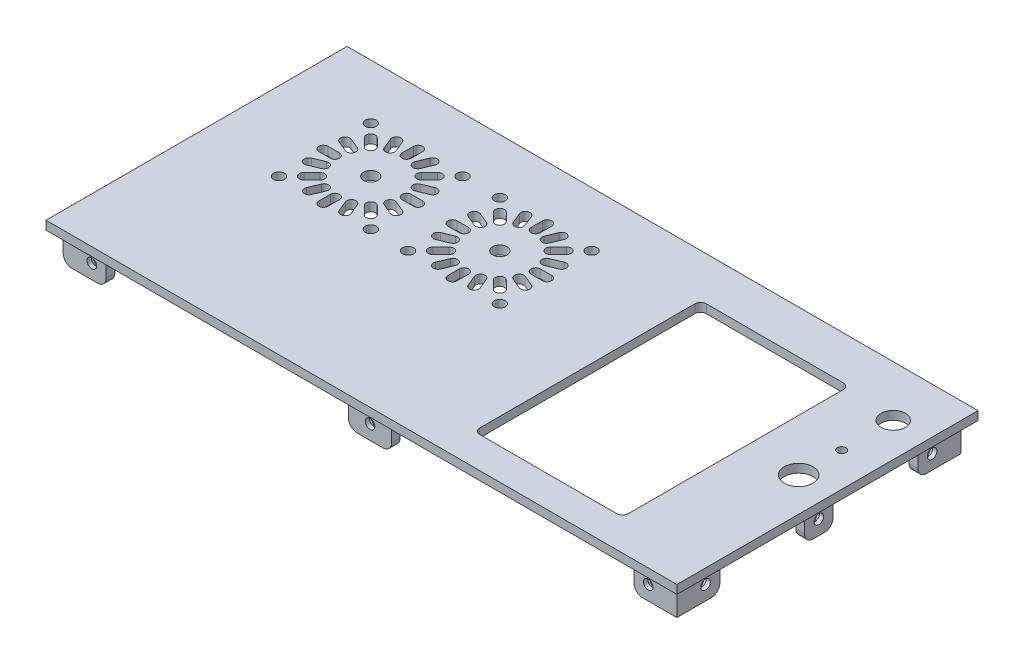
SolidWorks part; units mm, degrees
ref_plane "Ön Düzlem" through (0, 0, 0) normal (0, 0, 1) x (1, 0, 0)
ref_plane "Üst Düzlem" through (0, 0, 0) normal (0, 1, 0) x (1, 0, 0)
ref_plane "Sağ Düzlem" through (0, 0, 0) normal (1, 0, 0) x (0, 0, -1)
sketch "Çizim1" plane through (0, 0, 0) normal (0, 1, 0) x (1, 0, 0)
  line L0 (-66.65, 17.4) -> (49933.35, 17.4) construction
  line L1 (-110, -52.5) -> (110, -52.5)
  line L2 (-110, -52.5) -> (-110, 52.5)
  line L3 (-110, 52.5) -> (110, 52.5)
  line L4 (110, -52.5) -> (110, 52.5)
  line L5 (-110, -52.5) -> (110, 52.5) construction
  line L6 (-110, 52.5) -> (110, -52.5) construction
  line L7 (78.15, 37.4) -> (30.35, 37.4)
  line L8 (80.15, 35.4) -> (80.15, -39.6)
  line L9 (78.15, -41.6) -> (30.35, -41.6)
  line L10 (28.35, 35.4) -> (28.35, -39.6)
  line L11 (80.15, 37.4) -> (28.35, -41.6) construction
  line L12 (80.15, -41.6) -> (28.35, 37.4) construction
  line L13 (-66.65, 17.4) -> (-66.65, 50017.4) construction
  line L14 (-44.15, 43.0126) -> (-44.15, -49956.9874) construction
  line L15 (-66.65, 17.4) -> (35288.6891, -35337.9391) construction
  line L16 (-66.65, 17.4) -> (35288.6891, 35372.7391) construction
  line L17 (-66.65, 17.4) -> (19067.5216, -46176.5766) construction
  line L18 (-66.65, 17.4) -> (19067.5216, 46211.3766) construction
  line L19 (-66.65, 17.4) -> (46127.3266, -19116.7716) construction
  line L20 (-66.65, 17.4) -> (46127.3266, 19151.5716) construction
  line L21 (-66.65, 29.9) -> (-66.65, 33.9) construction
  line L22 (-68.25, 29.9) -> (-68.25, 33.9)
  line L23 (-65.05, 29.9) -> (-65.05, 33.9)
  line L24 (-71.4335, 28.9485) -> (-72.9643, 32.644) construction
  line L25 (-72.9118, 28.3362) -> (-74.4425, 32.0317)
  line L26 (-69.9553, 29.5608) -> (-71.4861, 33.2563)
  line L27 (-79.15, 17.4) -> (-83.15, 17.4) construction
  line L28 (-79.15, 19) -> (-83.15, 19)
  line L29 (-79.15, 15.8) -> (-83.15, 15.8)
  line L30 (-78.1985, 22.1835) -> (-81.894, 23.7143) construction
  line L31 (-77.5862, 23.6618) -> (-81.2817, 25.1925)
  line L32 (-78.8108, 20.7053) -> (-82.5063, 22.2361)
  line L33 (-75.4888, 26.2388) -> (-78.3173, 29.0673) construction
  line L34 (-74.3575, 27.3702) -> (-77.1859, 30.1986)
  line L35 (-76.6202, 25.1075) -> (-79.4486, 27.9359)
  line L36 (-78.1985, 12.6165) -> (-81.894, 11.0857) construction
  line L37 (-77.5862, 11.1382) -> (-81.2817, 9.6075)
  line L38 (-78.8108, 14.0947) -> (-82.5063, 12.5639)
  line L39 (-75.4888, 8.5612) -> (-78.3173, 5.7327) construction
  line L40 (-74.3575, 7.4298) -> (-77.1859, 4.6014)
  line L41 (-76.6202, 9.6925) -> (-79.4486, 6.8641)
  line L42 (-71.4335, 5.8515) -> (-72.9643, 2.156) construction
  line L43 (-72.9118, 6.4638) -> (-74.4425, 2.7683)
  line L44 (-69.9553, 5.2392) -> (-71.4861, 1.5437)
  line L45 (-66.65, 4.9) -> (-66.65, 0.9) construction
  line L46 (-68.25, 4.9) -> (-68.25, 0.9)
  line L47 (-65.05, 4.9) -> (-65.05, 0.9)
  line L48 (-54.15, 17.4) -> (-50.15, 17.4) construction
  line L49 (-54.15, 19) -> (-50.15, 19)
  line L50 (-54.15, 15.8) -> (-50.15, 15.8)
  line L51 (-55.1015, 22.1835) -> (-51.406, 23.7143) construction
  line L52 (-55.7138, 23.6618) -> (-52.0183, 25.1925)
  line L53 (-54.4892, 20.7053) -> (-50.7937, 22.2361)
  line L54 (-57.8112, 26.2388) -> (-54.9827, 29.0673) construction
  line L55 (-58.9425, 27.3702) -> (-56.1141, 30.1986)
  line L56 (-56.6798, 25.1075) -> (-53.8514, 27.9359)
  line L57 (-61.8665, 28.9485) -> (-60.3357, 32.644) construction
  line L58 (-60.3882, 28.3362) -> (-58.8575, 32.0317)
  line L59 (-63.3447, 29.5608) -> (-61.8139, 33.2563)
  line L60 (-55.1015, 12.6165) -> (-51.406, 11.0857) construction
  line L61 (-55.7138, 11.1382) -> (-52.0183, 9.6075)
  line L62 (-54.4892, 14.0947) -> (-50.7937, 12.5639)
  line L63 (-57.8112, 8.5612) -> (-54.9827, 5.7327) construction
  line L64 (-58.9425, 7.4298) -> (-56.1141, 4.6014)
  line L65 (-56.6798, 9.6925) -> (-53.8514, 6.8641)
  line L66 (-61.8665, 5.8515) -> (-60.3357, 2.156) construction
  line L67 (-60.3882, 6.4638) -> (-58.8575, 2.7683)
  line L68 (-63.3447, 5.2392) -> (-61.8139, 1.5437)
  line L69 (-16.8665, 28.9485) -> (-15.3357, 32.644) construction
  line L70 (-15.3882, 28.3362) -> (-13.8575, 32.0317)
  line L71 (-18.3447, 29.5608) -> (-16.8139, 33.2563)
  line L72 (-12.8112, 26.2388) -> (-9.9827, 29.0673) construction
  line L73 (-13.9425, 27.3702) -> (-11.1141, 30.1986)
  line L74 (-11.6798, 25.1075) -> (-8.8514, 27.9359)
  line L75 (-10.1015, 22.1835) -> (-6.406, 23.7143) construction
  line L76 (-10.7138, 23.6618) -> (-7.0183, 25.1925)
  line L77 (-9.4892, 20.7053) -> (-5.7937, 22.2361)
  line L78 (-9.15, 17.4) -> (-5.15, 17.4) construction
  line L79 (-9.15, 19) -> (-5.15, 19)
  line L80 (-9.15, 15.8) -> (-5.15, 15.8)
  line L81 (-10.1015, 12.6165) -> (-6.406, 11.0857) construction
  line L82 (-10.7138, 11.1382) -> (-7.0183, 9.6075)
  line L83 (-9.4892, 14.0947) -> (-5.7937, 12.5639)
  line L84 (-12.8112, 8.5612) -> (-9.9827, 5.7327) construction
  line L85 (-13.9425, 7.4298) -> (-11.1141, 4.6014)
  line L86 (-11.6798, 9.6925) -> (-8.8514, 6.8641)
  line L87 (-16.8665, 5.8515) -> (-15.3357, 2.156) construction
  line L88 (-15.3882, 6.4638) -> (-13.8575, 2.7683)
  line L89 (-18.3447, 5.2392) -> (-16.8139, 1.5437)
  line L90 (-21.65, 4.9) -> (-21.65, 0.9) construction
  line L91 (-20.05, 4.9) -> (-20.05, 0.9)
  line L92 (-23.25, 4.9) -> (-23.25, 0.9)
  line L93 (-21.65, 29.9) -> (-21.65, 33.9) construction
  line L94 (-20.05, 29.9) -> (-20.05, 33.9)
  line L95 (-23.25, 29.9) -> (-23.25, 33.9)
  line L96 (-26.4335, 5.8515) -> (-27.9643, 2.156) construction
  line L97 (-27.9118, 6.4638) -> (-29.4425, 2.7683)
  line L98 (-24.9553, 5.2392) -> (-26.4861, 1.5437)
  line L99 (-30.4888, 8.5612) -> (-33.3173, 5.7327) construction
  line L100 (-29.3575, 7.4298) -> (-32.1859, 4.6014)
  line L101 (-31.6202, 9.6925) -> (-34.4486, 6.8641)
  line L102 (-33.1985, 12.6165) -> (-36.894, 11.0857) construction
  line L103 (-32.5862, 11.1382) -> (-36.2817, 9.6075)
  line L104 (-33.8108, 14.0947) -> (-37.5063, 12.5639)
  line L105 (-34.15, 17.4) -> (-38.15, 17.4) construction
  line L106 (-34.15, 19) -> (-38.15, 19)
  line L107 (-34.15, 15.8) -> (-38.15, 15.8)
  line L108 (-33.1985, 22.1835) -> (-36.894, 23.7143) construction
  line L109 (-32.5862, 23.6618) -> (-36.2817, 25.1925)
  line L110 (-33.8108, 20.7053) -> (-37.5063, 22.2361)
  line L111 (-30.4888, 26.2388) -> (-33.3173, 29.0673) construction
  line L112 (-29.3575, 27.3702) -> (-32.1859, 30.1986)
  line L113 (-31.6202, 25.1075) -> (-34.4486, 27.9359)
  line L114 (-26.4335, 28.9485) -> (-27.9643, 32.644) construction
  line L115 (-27.9118, 28.3362) -> (-29.4425, 32.0317)
  line L116 (-24.9553, 29.5608) -> (-26.4861, 33.2563)
  circle A0 centre (98.15, 34.8) radius 4.25
  circle A1 centre (98.15, 1.8) radius 5
  circle A2 centre (98.15, 16.8) radius 1.5
  arc A3 (-15.3882, 28.3362) -> (-18.3447, 29.5608) centre (-16.8665, 28.9485) cw
  circle A5 centre (-82.65, 33.4) radius 1.9
  circle A6 centre (-50.65, 33.4) radius 1.9
  circle A7 centre (-37.65, 33.4) radius 1.9
  circle A8 centre (-5.65, 33.4) radius 1.9
  circle A9 centre (-5.65, 1.4) radius 1.9
  circle A10 centre (-37.65, 1.4) radius 1.9
  circle A11 centre (-50.65, 1.4) radius 1.9
  circle A12 centre (-82.65, 1.4) radius 1.9
  arc A13 (80.15, -39.6) -> (78.15, -41.6) centre (78.15, -39.6) cw
  arc A14 (30.35, -41.6) -> (28.35, -39.6) centre (30.35, -39.6) cw
  arc A15 (80.15, 35.4) -> (78.15, 37.4) centre (78.15, 35.4) ccw
  arc A16 (30.35, 37.4) -> (28.35, 35.4) centre (30.35, 35.4) ccw
  arc A17 (-16.8139, 33.2563) -> (-13.8575, 32.0317) centre (-15.3357, 32.644) cw
  arc A18 (-13.9425, 27.3702) -> (-11.6798, 25.1075) centre (-12.8112, 26.2388) ccw
  arc A19 (-68.25, 29.9) -> (-65.05, 29.9) centre (-66.65, 29.9) ccw
  arc A20 (-65.05, 33.9) -> (-68.25, 33.9) centre (-66.65, 33.9) ccw
  arc A21 (-72.9118, 28.3362) -> (-69.9553, 29.5608) centre (-71.4335, 28.9485) ccw
  arc A22 (-71.4861, 33.2563) -> (-74.4425, 32.0317) centre (-72.9643, 32.644) ccw
  arc A23 (-79.15, 19) -> (-79.15, 15.8) centre (-79.15, 17.4) cw
  arc A24 (-83.15, 15.8) -> (-83.15, 19) centre (-83.15, 17.4) cw
  arc A25 (-77.5862, 23.6618) -> (-78.8108, 20.7053) centre (-78.1985, 22.1835) cw
  arc A26 (-82.5063, 22.2361) -> (-81.2817, 25.1925) centre (-81.894, 23.7143) cw
  arc A27 (-74.3575, 27.3702) -> (-76.6202, 25.1075) centre (-75.4888, 26.2388) cw
  arc A28 (-79.4486, 27.9359) -> (-77.1859, 30.1986) centre (-78.3173, 29.0673) cw
  arc A29 (-77.5862, 11.1382) -> (-78.8108, 14.0947) centre (-78.1985, 12.6165) ccw
  arc A30 (-82.5063, 12.5639) -> (-81.2817, 9.6075) centre (-81.894, 11.0857) ccw
  arc A31 (-74.3575, 7.4298) -> (-76.6202, 9.6925) centre (-75.4888, 8.5612) ccw
  arc A32 (-79.4486, 6.8641) -> (-77.1859, 4.6014) centre (-78.3173, 5.7327) ccw
  arc A33 (-72.9118, 6.4638) -> (-69.9553, 5.2392) centre (-71.4335, 5.8515) cw
  arc A34 (-71.4861, 1.5437) -> (-74.4425, 2.7683) centre (-72.9643, 2.156) cw
  arc A35 (-68.25, 4.9) -> (-65.05, 4.9) centre (-66.65, 4.9) cw
  arc A36 (-65.05, 0.9) -> (-68.25, 0.9) centre (-66.65, 0.9) cw
  arc A37 (-54.15, 19) -> (-54.15, 15.8) centre (-54.15, 17.4) ccw
  arc A38 (-50.15, 15.8) -> (-50.15, 19) centre (-50.15, 17.4) ccw
  arc A39 (-55.7138, 23.6618) -> (-54.4892, 20.7053) centre (-55.1015, 22.1835) ccw
  arc A40 (-50.7937, 22.2361) -> (-52.0183, 25.1925) centre (-51.406, 23.7143) ccw
  arc A41 (-58.9425, 27.3702) -> (-56.6798, 25.1075) centre (-57.8112, 26.2388) ccw
  arc A42 (-53.8514, 27.9359) -> (-56.1141, 30.1986) centre (-54.9827, 29.0673) ccw
  arc A43 (-60.3882, 28.3362) -> (-63.3447, 29.5608) centre (-61.8665, 28.9485) cw
  arc A44 (-61.8139, 33.2563) -> (-58.8575, 32.0317) centre (-60.3357, 32.644) cw
  arc A45 (-55.7138, 11.1382) -> (-54.4892, 14.0947) centre (-55.1015, 12.6165) cw
  arc A46 (-50.7937, 12.5639) -> (-52.0183, 9.6075) centre (-51.406, 11.0857) cw
  arc A47 (-58.9425, 7.4298) -> (-56.6798, 9.6925) centre (-57.8112, 8.5612) cw
  arc A48 (-53.8514, 6.8641) -> (-56.1141, 4.6014) centre (-54.9827, 5.7327) cw
  arc A49 (-60.3882, 6.4638) -> (-63.3447, 5.2392) centre (-61.8665, 5.8515) ccw
  arc A50 (-61.8139, 1.5437) -> (-58.8575, 2.7683) centre (-60.3357, 2.156) ccw
  circle A51 centre (-66.65, 17.4) radius 2.5
  arc A52 (-8.8514, 27.9359) -> (-11.1141, 30.1986) centre (-9.9827, 29.0673) ccw
  arc A53 (-10.7138, 23.6618) -> (-9.4892, 20.7053) centre (-10.1015, 22.1835) ccw
  arc A54 (-5.7937, 22.2361) -> (-7.0183, 25.1925) centre (-6.406, 23.7143) ccw
  arc A55 (-9.15, 19) -> (-9.15, 15.8) centre (-9.15, 17.4) ccw
  arc A56 (-5.15, 15.8) -> (-5.15, 19) centre (-5.15, 17.4) ccw
  arc A57 (-10.7138, 11.1382) -> (-9.4892, 14.0947) centre (-10.1015, 12.6165) cw
  arc A58 (-5.7937, 12.5639) -> (-7.0183, 9.6075) centre (-6.406, 11.0857) cw
  arc A59 (-13.9425, 7.4298) -> (-11.6798, 9.6925) centre (-12.8112, 8.5612) cw
  arc A60 (-8.8514, 6.8641) -> (-11.1141, 4.6014) centre (-9.9827, 5.7327) cw
  arc A61 (-15.3882, 6.4638) -> (-18.3447, 5.2392) centre (-16.8665, 5.8515) ccw
  arc A62 (-16.8139, 1.5437) -> (-13.8575, 2.7683) centre (-15.3357, 2.156) ccw
  arc A63 (-20.05, 4.9) -> (-23.25, 4.9) centre (-21.65, 4.9) ccw
  arc A64 (-23.25, 0.9) -> (-20.05, 0.9) centre (-21.65, 0.9) ccw
  arc A65 (-20.05, 29.9) -> (-23.25, 29.9) centre (-21.65, 29.9) cw
  arc A66 (-23.25, 33.9) -> (-20.05, 33.9) centre (-21.65, 33.9) cw
  arc A67 (-27.9118, 6.4638) -> (-24.9553, 5.2392) centre (-26.4335, 5.8515) cw
  arc A68 (-26.4861, 1.5437) -> (-29.4425, 2.7683) centre (-27.9643, 2.156) cw
  arc A69 (-29.3575, 7.4298) -> (-31.6202, 9.6925) centre (-30.4888, 8.5612) ccw
  arc A70 (-34.4486, 6.8641) -> (-32.1859, 4.6014) centre (-33.3173, 5.7327) ccw
  arc A71 (-32.5862, 11.1382) -> (-33.8108, 14.0947) centre (-33.1985, 12.6165) ccw
  arc A72 (-37.5063, 12.5639) -> (-36.2817, 9.6075) centre (-36.894, 11.0857) ccw
  arc A73 (-34.15, 19) -> (-34.15, 15.8) centre (-34.15, 17.4) cw
  arc A74 (-38.15, 15.8) -> (-38.15, 19) centre (-38.15, 17.4) cw
  arc A75 (-32.5862, 23.6618) -> (-33.8108, 20.7053) centre (-33.1985, 22.1835) cw
  arc A76 (-37.5063, 22.2361) -> (-36.2817, 25.1925) centre (-36.894, 23.7143) cw
  arc A77 (-29.3575, 27.3702) -> (-31.6202, 25.1075) centre (-30.4888, 26.2388) cw
  arc A78 (-34.4486, 27.9359) -> (-32.1859, 30.1986) centre (-33.3173, 29.0673) cw
  arc A79 (-27.9118, 28.3362) -> (-24.9553, 29.5608) centre (-26.4335, 28.9485) ccw
  arc A80 (-26.4861, 33.2563) -> (-29.4425, 32.0317) centre (-27.9643, 32.644) ccw
  circle A81 centre (-21.65, 17.4) radius 2.5
  point P0 (0, 0)
  point P6 (54.25, -2.1)
  point P50 (-16.1011, 30.7963)
  point P71 (-66.65, 31.9)
  point P78 (-72.1989, 30.7963)
  point P85 (-81.15, 17.4)
  point P92 (-80.0463, 22.9489)
  point P99 (-76.903, 27.653)
  point P106 (-80.0463, 11.8511)
  point P113 (-76.903, 7.147)
  point P120 (-72.1989, 4.0037)
  point P127 (-66.65, 2.9)
  point P134 (-52.15, 17.4)
  point P141 (-53.2537, 22.9489)
  point P148 (-56.397, 27.653)
  point P155 (-61.1011, 30.7963)
  point P162 (-53.2537, 11.8511)
  point P169 (-56.397, 7.147)
  point P176 (-61.1011, 4.0037)
  point P188 (-11.397, 27.653)
  point P195 (-8.2537, 22.9489)
  point P202 (-7.15, 17.4)
  point P209 (-8.2537, 11.8511)
  point P216 (-11.397, 7.147)
  point P223 (-16.1011, 4.0037)
  point P230 (-21.65, 2.9)
  point P237 (-21.65, 31.9)
  point P244 (-27.1989, 4.0037)
  point P251 (-31.903, 7.147)
  point P258 (-35.0463, 11.8511)
  point P265 (-36.15, 17.4)
  point P272 (-35.0463, 22.9489)
  point P279 (-31.903, 27.653)
  point P286 (-27.1989, 30.7963)
  dimension "D7" = 8.5
  dimension "D11" = 3
  dimension "D12" = 10
  dimension "D15" = 5
  dimension "D19" = 3.8
  dimension "D20" = 3.8
  dimension "D21" = 3.8
  dimension "D22" = 3.8
  dimension "D23" = 3.8
  dimension "D24" = 3.8
  dimension "D25" = 3.8
  dimension "D26" = 3.8
  dimension "D38" = 2
  dimension "D45" = 1.6
  dimension "D46" = 1.6
  dimension "D47" = 5
  dimension "D1" = 105
  dimension "D3" = 79
  dimension "D4" = 51.8
  dimension "D5" = 55.75
  dimension "D6" = 18
  dimension "D8" = 2.6
  dimension "D9" = 33
  dimension "D10" = 18
  dimension "D13" = 220
  dimension "D14" = 45
  dimension "D17" = 50
  dimension "D18" = 20
  dimension "D27" = 32
  dimension "D28" = 32
  dimension "D29" = 32
  dimension "D30" = 32
  dimension "D31" = 32
  dimension "D32" = 32
  dimension "D33" = 16
  dimension "D34" = 16
  dimension "D35" = 16
  dimension "D36" = 16
  dimension "D37" = 50.4
  dimension "D41" = 22.5
  dimension "D42" = 22.5
  dimension "D43" = 22.5
  dimension "D44" = 22.5
extrude "Yükseklik-Ekstrüzyon1" add sketch "Çizim1" along normal blind 3
sketch "Çizim2" plane through (0, 0, 0) normal (0, -1, 0) x (1, 0, 0)
  line L0 (-110, -52.5) -> (-110, 52.5) construction
  line L1 (92, 49.5) -> (107, 49.5)
  line L2 (107, 49.5) -> (107, 34.5)
  line L3 (107, 34.5) -> (104, 34.5)
  line L4 (104, 34.5) -> (104, 46.5)
  line L5 (104, 46.5) -> (92, 46.5)
  line L6 (92, 46.5) -> (92, 49.5)
  line L7 (-110, 52.5) -> (110, 52.5) construction
  line L8 (110, 52.5) -> (110, -52.5) construction
  line L9 (0, 0) -> (0, 50000) construction
  line L10 (0, 0) -> (50000, 0) construction
  line L11 (107, -34.5) -> (104, -34.5)
  line L12 (107, -49.5) -> (107, -34.5)
  line L13 (104, -34.5) -> (104, -46.5)
  line L14 (104, -46.5) -> (92, -46.5)
  line L15 (92, -46.5) -> (92, -49.5)
  line L16 (92, -49.5) -> (107, -49.5)
  line L17 (-92, -49.5) -> (-107, -49.5)
  line L18 (-92, -46.5) -> (-92, -49.5)
  line L19 (-104, -46.5) -> (-92, -46.5)
  line L20 (-104, -34.5) -> (-104, -46.5)
  line L21 (-107, -49.5) -> (-107, -34.5)
  line L22 (-107, -34.5) -> (-104, -34.5)
  line L23 (-92, 46.5) -> (-92, 49.5)
  line L24 (-104, 46.5) -> (-92, 46.5)
  line L25 (-104, 34.5) -> (-104, 46.5)
  line L26 (-107, 34.5) -> (-104, 34.5)
  line L27 (-107, 49.5) -> (-107, 34.5)
  line L28 (-92, 49.5) -> (-107, 49.5)
  line L29 (7.5, -49.5) -> (-7.5, -46.5) construction
  line L30 (7.5, 49.5) -> (-7.5, 49.5)
  line L31 (7.5, 49.5) -> (7.5, 46.5)
  line L32 (7.5, 46.5) -> (-7.5, 46.5)
  line L33 (-7.5, 49.5) -> (-7.5, 46.5)
  line L34 (7.5, 49.5) -> (-7.5, 46.5) construction
  line L35 (7.5, 46.5) -> (-7.5, 49.5) construction
  line L36 (7.5, -46.5) -> (-7.5, -49.5) construction
  line L37 (-7.5, -49.5) -> (-7.5, -46.5)
  line L38 (7.5, -46.5) -> (-7.5, -46.5)
  line L39 (7.5, -49.5) -> (7.5, -46.5)
  line L40 (7.5, -49.5) -> (-7.5, -49.5)
  line L41 (-104, 5) -> (-107, 5)
  line L42 (-104, 5) -> (-104, -5)
  line L43 (-104, -5) -> (-107, -5)
  line L44 (-107, 5) -> (-107, -5)
  line L45 (-104, 5) -> (-107, -5) construction
  line L46 (-104, -5) -> (-107, 5) construction
  line L48 (107, 5) -> (104, 5)
  line L49 (107, 5) -> (107, -5)
  line L50 (107, -5) -> (104, -5)
  line L51 (104, 5) -> (104, -5)
  line L52 (107, 5) -> (104, -5) construction
  line L53 (107, -5) -> (104, 5) construction
  point P33 (0, 48)
  point P38 (0, -48)
  point P43 (-105.5, 0)
  point P50 (105.5, 0)
  dimension "D1" = 3
  dimension "D2" = 3
  dimension "D3" = 3
  dimension "D4" = 3
  dimension "D5" = 15
  dimension "D6" = 15
  dimension "D7" = 3
  dimension "D8" = 15
  dimension "D9" = 3
  dimension "D10" = 3
  dimension "D11" = 3
  dimension "D12" = 10
  dimension "D13" = 3
  dimension "D14" = 10
  dimension "D15" = 3
extrude "Yükseklik-Ekstrüzyon3" add sketch "Çizim2" along normal blind 10
sketch "Çizim3" plane through (0, 0, 49.5) normal (0, 0, 1) x (1, 0, 0)
  line L0 (-110, 0) -> (110, 0) construction
  line L1 (-92, -10) -> (-92, 0) construction
  line L2 (7.5, -10) -> (7.5, 0) construction
  line L3 (7.5, -10) -> (-7.5, -10) construction
  line L4 (92, -10) -> (92, 0) construction
  line L5 (107, -10) -> (92, -10) construction
  circle A0 centre (-97, -5) radius 1.675
  circle A1 centre (0, -5) radius 1.675
  circle A2 centre (97, -5) radius 1.675
  point P10 (7.5, -5)
  dimension "D1" = 3.35
  dimension "D4" = 3.35
  dimension "D5" = 7.5
  dimension "D7" = 3.35
  dimension "D2" = 5
  dimension "D3" = 5
  dimension "D6" = 5
  dimension "D8" = 5
  dimension "D9" = 5
extrude "Kes-Ekstrüzyon1" cut sketch "Çizim3" against normal blind 120
sketch "Çizim4" plane through (-107, 0, 0) normal (-1, 0, 0) x (0, 0, 1)
  line L0 (49.5, -10) -> (34.5, -10) construction
  line L1 (34.5, -10) -> (34.5, 0) construction
  line L2 (-34.5, -10) -> (-49.5, -10) construction
  line L3 (-34.5, -10) -> (-34.5, 0) construction
  line L4 (-5, -10) -> (-5, 0) construction
  line L5 (-5, -10) -> (5, -10) construction
  circle A0 centre (39.5, -5) radius 1.675
  circle A1 centre (-39.5, -5) radius 1.675
  circle A2 centre (0, -5) radius 1.675
  dimension "D1" = 3.35
  dimension "D6" = 3.35
  dimension "D7" = 3.35
  dimension "D2" = 5
  dimension "D3" = 5
  dimension "D4" = 5
  dimension "D5" = 5
  dimension "D8" = 5
  dimension "D9" = 5
extrude "Kes-Ekstrüzyon2" cut sketch "Çizim4" against normal blind 215
sketch "Çizim5" plane through (0, 0, -49.5) normal (0, 0, -1) x (-1, 0, 0)
  line L0 (107, -10) -> (107, 0) construction
  line L1 (107, -10) -> (92, -10) construction
  line L3 (92, 0) -> (99.5, 0)
  line L4 (92, 0) -> (92, -10)
  line L5 (92, -10) -> (99.5, -10)
  line L6 (99.5, 0) -> (99.5, -10)
  circle A0 centre (102, -5) radius 1.675
  dimension "D3" = 3.35
  dimension "D1" = 5
  dimension "D2" = 5
extrude "Kes-Ekstrüzyon3" cut sketch "Çizim5" against normal blind 3
sketch "Çizim6" plane through (-107, 0, 0) normal (-1, 0, 0) x (0, 0, 1)
  line L0 (49.5, -10) -> (34.5, -10) construction
  line L1 (34.5, 0) -> (46.5, 0)
  line L2 (34.5, 0) -> (34.5, -10)
  line L3 (34.5, -10) -> (46.5, -10)
  line L4 (46.5, 0) -> (46.5, -10)
  line L5 (52.5, 3) -> (52.5, 0) construction
  dimension "D1" = 6
extrude "Kes-Ekstrüzyon4" cut sketch "Çizim6" against normal blind 3
fillet "Radyus1" radius 3 16 edges at (92, -10, -48) (105.5, -10, -34.5) (105.5, -10, -5) (105.5, -10, 5) (105.5, -10, 34.5) (92, -10, 48) (7.5, -10, 48) (-7.5, -10, 48) (7.5, -10, -48) (-7.5, -10, -48) (-92, -10, 48) (-107, -10, 48) (-99.5, -10, -48) (-105.5, -10, -5) (-105.5, -10, 5) (-105.5, -10, -34.5)
sketch "Çizim7" plane through (0, 0, -46.5) normal (0, 0, 1) x (1, 0, 0)
  line L1 (3.25, -5) -> (1.625, -2.1854)
  line L2 (1.625, -2.1854) -> (-1.625, -2.1854)
  line L3 (-1.625, -2.1854) -> (-3.25, -5)
  line L4 (-3.25, -5) -> (-1.625, -7.8146)
  line L5 (-1.625, -7.8146) -> (1.625, -7.8146)
  line L6 (1.625, -7.8146) -> (3.25, -5)
  line L7 (100.25, -5) -> (98.625, -2.1854)
  line L8 (98.625, -2.1854) -> (95.375, -2.1854)
  line L9 (95.375, -2.1854) -> (93.75, -5)
  line L10 (93.75, -5) -> (95.375, -7.8146)
  line L11 (95.375, -7.8146) -> (98.625, -7.8146)
  line L12 (98.625, -7.8146) -> (100.25, -5)
  line L13 (-98.75, -5) -> (-100.375, -2.1854)
  line L14 (-100.375, -2.1854) -> (-103.625, -2.1854)
  line L15 (-103.625, -2.1854) -> (-105.25, -5)
  line L16 (-105.25, -5) -> (-103.625, -7.8146)
  line L17 (-103.625, -7.8146) -> (-100.375, -7.8146)
  line L18 (-100.375, -7.8146) -> (-98.75, -5)
  circle A0 centre (0, -5) radius 3.25 construction
  circle A1 centre (97, -5) radius 3.25 construction
  circle A2 centre (-102, -5) radius 3.25 construction
  dimension "D1" = 6.5
  dimension "D2" = 6.5
  dimension "D3" = 6.5
extrude "Kes-Ekstrüzyon5" cut sketch "Çizim7" against normal blind 1.5
sketch "Çizim8" plane through (104, 0, 0) normal (-1, 0, 0) x (0, 0, 1)
  line L1 (3.25, -5) -> (1.625, -2.1854)
  line L2 (1.625, -2.1854) -> (-1.625, -2.1854)
  line L3 (-1.625, -2.1854) -> (-3.25, -5)
  line L4 (-3.25, -5) -> (-1.625, -7.8146)
  line L5 (-1.625, -7.8146) -> (1.625, -7.8146)
  line L6 (1.625, -7.8146) -> (3.25, -5)
  line L7 (-36.25, -5) -> (-37.875, -2.1854)
  line L8 (-37.875, -2.1854) -> (-41.125, -2.1854)
  line L9 (-41.125, -2.1854) -> (-42.75, -5)
  line L10 (-42.75, -5) -> (-41.125, -7.8146)
  line L11 (-41.125, -7.8146) -> (-37.875, -7.8146)
  line L12 (-37.875, -7.8146) -> (-36.25, -5)
  line L13 (42.75, -5) -> (41.125, -2.1854)
  line L14 (41.125, -2.1854) -> (37.875, -2.1854)
  line L15 (37.875, -2.1854) -> (36.25, -5)
  line L16 (36.25, -5) -> (37.875, -7.8146)
  line L17 (37.875, -7.8146) -> (41.125, -7.8146)
  line L18 (41.125, -7.8146) -> (42.75, -5)
  circle A0 centre (0, -5) radius 3.25 construction
  circle A1 centre (-39.5, -5) radius 3.25 construction
  circle A2 centre (39.5, -5) radius 3.25 construction
  dimension "D1" = 6.5
  dimension "D2" = 6.5
  dimension "D3" = 6.5
extrude "Kes-Ekstrüzyon6" cut sketch "Çizim8" against normal blind 1.5
sketch "Çizim9" plane through (0, 0, 46.5) normal (0, 0, -1) x (-1, 0, 0)
  line L1 (3.25, -5) -> (1.625, -2.1854)
  line L2 (1.625, -2.1854) -> (-1.625, -2.1854)
  line L3 (-1.625, -2.1854) -> (-3.25, -5)
  line L4 (-3.25, -5) -> (-1.625, -7.8146)
  line L5 (-1.625, -7.8146) -> (1.625, -7.8146)
  line L6 (1.625, -7.8146) -> (3.25, -5)
  line L7 (100.25, -5) -> (98.625, -2.1854)
  line L8 (98.625, -2.1854) -> (95.375, -2.1854)
  line L9 (95.375, -2.1854) -> (93.75, -5)
  line L10 (93.75, -5) -> (95.375, -7.8146)
  line L11 (95.375, -7.8146) -> (98.625, -7.8146)
  line L12 (98.625, -7.8146) -> (100.25, -5)
  line L13 (-93.75, -5) -> (-95.375, -2.1854)
  line L14 (-95.375, -2.1854) -> (-98.625, -2.1854)
  line L15 (-98.625, -2.1854) -> (-100.25, -5)
  line L16 (-100.25, -5) -> (-98.625, -7.8146)
  line L17 (-98.625, -7.8146) -> (-95.375, -7.8146)
  line L18 (-95.375, -7.8146) -> (-93.75, -5)
  circle A0 centre (0, -5) radius 3.25 construction
  circle A1 centre (97, -5) radius 3.25 construction
  circle A2 centre (-97, -5) radius 3.25 construction
  dimension "D1" = 6.5
  dimension "D2" = 6.5
  dimension "D3" = 6.5
extrude "Kes-Ekstrüzyon7" cut sketch "Çizim9" against normal blind 1.5
sketch "Çizim10" plane through (-104, 0, 0) normal (1, 0, 0) x (0, 0, -1)
  line L1 (42.75, -5) -> (41.125, -2.1854)
  line L2 (41.125, -2.1854) -> (37.875, -2.1854)
  line L3 (37.875, -2.1854) -> (36.25, -5)
  line L4 (36.25, -5) -> (37.875, -7.8146)
  line L5 (37.875, -7.8146) -> (41.125, -7.8146)
  line L6 (41.125, -7.8146) -> (42.75, -5)
  line L7 (3.25, -5) -> (1.625, -2.1854)
  line L8 (1.625, -2.1854) -> (-1.625, -2.1854)
  line L9 (-1.625, -2.1854) -> (-3.25, -5)
  line L10 (-3.25, -5) -> (-1.625, -7.8146)
  line L11 (-1.625, -7.8146) -> (1.625, -7.8146)
  line L12 (1.625, -7.8146) -> (3.25, -5)
  circle A0 centre (39.5, -5) radius 3.25 construction
  circle A1 centre (0, -5) radius 3.25 construction
  dimension "D1" = 6.5
  dimension "D2" = 6.5
extrude "Kes-Ekstrüzyon8" cut sketch "Çizim10" against normal blind 1.5
chamfer "Pah1" distance 1 angle 45 26 edges at (-104, 0, -40.5) (-101.75, 0, -46.5) (-104, 0, 0) (0, 0, -46.5) (98, 0, -46.5) (104, 0, -40.5) (104, 0, 0) (98, 0, 46.5) (104, 0, 40.5) (0, 0, 46.5) (-99.5, 0, 46.5) (-105.5, 0, -34.5) (-99.5, 0, -48) (-105.5, 0, -5) (-105.5, 0, 5) (7.5, 0, -48) (-7.5, 0, -48) (92, 0, -48) (105.5, 0, -34.5) (105.5, 0, -5) (105.5, 0, 5) (92, 0, 48) (105.5, 0, 34.5) (7.5, 0, 48) (-92, 0, 48) (-7.5, 0, 48)
